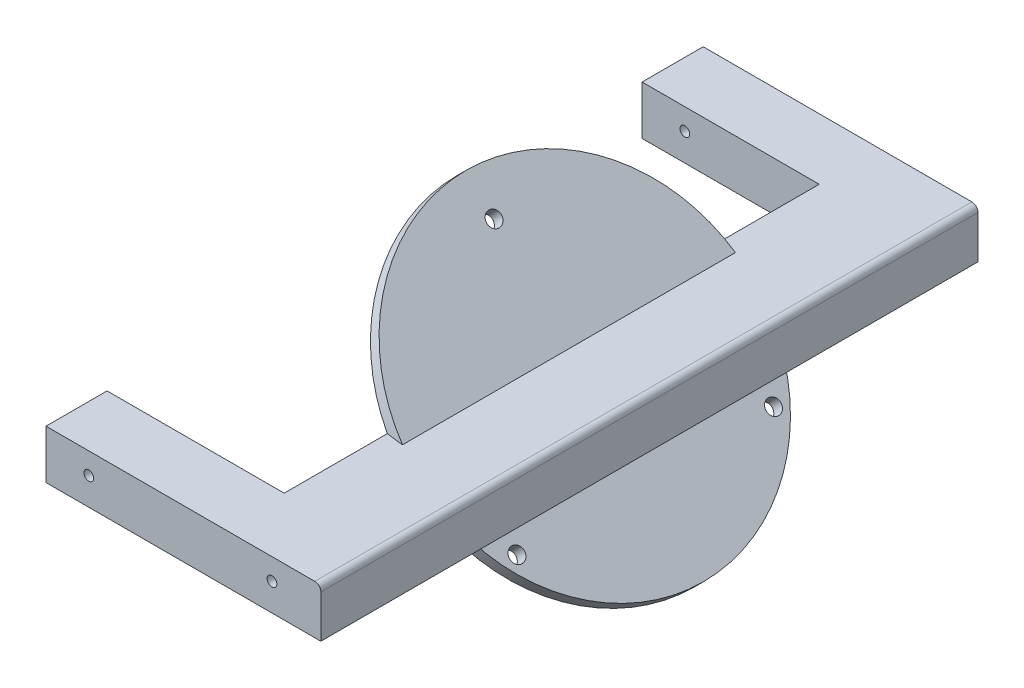
SolidWorks part; units mm, degrees
material "Nylon 101"
ref_plane "Front Plane" through (0, 0, 0) normal (0, 0, 1) x (1, 0, 0)
ref_plane "Top Plane" through (0, 0, 0) normal (0, 1, 0) x (1, 0, 0)
ref_plane "Right Plane" through (0, 0, 0) normal (1, 0, 0) x (0, 0, -1)
sketch "Sketch1" plane through (0, 0, 0) normal (0, 0, 1) x (1, 0, 0)
  line L4 (8, 4) -> (-8, 4)
  line L6 (0, -4) -> (-8, 4)
  line L7 (0, 4) -> (0, -4) construction
  line L8 (8, 4) -> (8, -4)
  line L9 (8, -4) -> (0, -4)
  dimension "D1" = 8
  dimension "D2" = 45
extrude "Base" add sketch "Sketch1" along normal mid plane 107.6
sketch "Sketch4" plane through (-2, -2, 0) normal (-0.7071, -0.7071, 0) x (0, 0, 1)
  line L0 (-53.8, 2.8284) -> (53.8, 2.8284) construction
  line L1 (-53.8, 8.4853) -> (-53.8, -2.8284) construction
  line L2 (53.8, 8.4853) -> (53.8, -2.8284) construction
  line L3 (0, 8.4853) -> (0, -2.8284) construction
  line L4 (53.8, 8.4853) -> (-53.8, 8.4853) construction
  line L6 (53.8, -2.8284) -> (-53.8, -2.8284) construction
  line L7 (-17.5, 20.3284) -> (17.5, 20.3284)
  line L8 (-17.5, 20.3284) -> (-17.5, -14.6716)
  line L9 (-17.5, -14.6716) -> (17.5, -14.6716)
  line L10 (17.5, 20.3284) -> (17.5, -14.6716)
  line L11 (-17.5, 20.3284) -> (17.5, -14.6716) construction
  line L12 (-17.5, -14.6716) -> (17.5, 20.3284) construction
  circle A0 centre (0, 2.8284) radius 27.5
  point P16 (0, 2.8284)
  point P17 (0, 2.8284)
  line M5 (53.8, 8.4853) -> (-53.8, 8.4853)
  dimension "D1" = 55
  dimension "D2" = 35
extrude "Boss-Extrude2" add sketch "Sketch4" against normal blind 2 contours A0 L8 L7 L10 M5 | L10 L7 L8 M5 | A0 L10 L9 L8 | A0 L8 M5 | L10 L8 L9 | L10 L8 M5 | A0 L10 M5 region at (-16.475, 12.475, 0) region at (-12.1872, 8.1872, 0) region at (0.1872, -4.1872, 0) region at (0.1872, -4.1872, -18.1422)
hole_wizard "M2 Clearance Hole1" positions "Sketch5" profile "Sketch6" hole size "M2" standard "ANSI Metric" end condition through all
sketch "Sketch5" plane through (-0.5858, -0.5858, 0) normal (0.7071, 0.7071, 0) x (0.7071, -0.7071, 0)
  line L4 (-8.4853, 0) -> (2.8284, 0) construction
  line L5 (-20.3284, 17.5) -> (-20.3284, -17.5) construction
  line L6 (-20.3284, -17.5) -> (14.6716, -17.5) construction
  line L7 (14.6716, 17.5) -> (14.6716, -17.5) construction
  line L8 (-20.3284, 17.5) -> (14.6716, 17.5) construction
  point P0 (-23.8284, 0)
  point P2 (11.1716, 21)
  point P4 (11.1716, -21)
  dimension "D1" = 3.5
  dimension "D2" = 3.5
  dimension "D3" = 3.5
  dimension "D4" = 3.5
sketch "Sketch6" plane through (-17.435, 16.2635, 0) normal (0, 0, 1) x (-0.7071, 0.7071, 0)
  line L0 (0, 0) -> (0, 29.5)
  line L1 (0, 29.5) -> (1.2, 29.5)
  line L2 (1.2, 29.5) -> (1.2, 0)
  line L5 (1.2, 0) -> (0, 0)
  line L11 (0, -6.35) -> (0, 107.95) construction
  dimension "Thru Hole Dia." = 2.4
  dimension "Thru Hole Depth" = 29.5
ref_plane "Plane1" through (-2, 2, 0) normal (0.7071, -0.7071, 0) x (0, 0, 1)
sketch "Sketch8" plane through (-2, 2, 0) normal (0.7071, -0.7071, 0) x (0, 0, 1)
  line L0 (0, 3.8284) -> (0, 2.8284)
  line L1 (27.5, 2.8284) -> (-27.5, 2.8284) construction
  line L2 (0, 2.8284) -> (-12, 2.8284)
  line L4 (0, 2.8284) -> (0, 10.3284) construction
  line L5 (-6.5, 10.3284) -> (-12, 2.8284)
  arc A1 (-6.5, 10.3284) -> (0, 3.8284) centre (0, 10.3284) ccw
  dimension "D2" = 6.5
  dimension "D1" = 1
  dimension "D3" = 12
revolve "Revolve1" add sketch "Sketch8" angle 360 about L4
fillet "Fillet1" radius 0.5 1 edges at (-13.8995, -0.7071, 0)
hole_wizard "Side Holes" positions "Sketch2" profile "Sketch3" hole size "M2x0.4" standard "ANSI Metric" end condition through all
sketch "Sketch2" plane through (0, 0, 53.8) normal (0, 0, 1) x (1, 0, 0)
  line L0 (0, 0.5) -> (0, 4) construction
  line L1 (8, 4) -> (-8, 4) construction
  line L3 (-4.5, 0.5) -> (8, 0.5) construction
  line L4 (-8, 4) -> (0, -4) construction
  line L6 (8, -4) -> (8, 4) construction
  point P0 (0, 0.5)
  dimension "D1" = 3.5
sketch "Sketch3" plane through (0, 0.5, 53.8) normal (1, 0, 0) x (0, -1, 0)
  line L0 (0, 0) -> (0, 107.6)
  line L1 (0, 107.6) -> (0.8, 107.6)
  line L2 (0.8, 107.6) -> (0.8, 0)
  line L5 (0.8, 0) -> (0, 0)
  line L11 (0, -6.35) -> (0, 107.95) construction
  dimension "Thru Hole Dia." = 1.6
  dimension "Thru Hole Depth" = 107.6
sketch "Sketch9" plane through (0, 0, 53.8) normal (0, 0, 1) x (1, 0, 0)
  line L0 (-8, 4) -> (0, -4)
  line L1 (0, -4) -> (-37, -4)
  line L2 (-37, -4) -> (-37, 4)
  line L3 (-37, 4) -> (-8, 4)
  line L4 (8, -4) -> (8, 4) construction
  dimension "D1" = 45
extrude "Side Arm" add sketch "Sketch9" against normal blind 10
mirror "Mirror1" about plane through (0, 0, 0) normal (0, 0, 1) of "Side Arm"
hole_wizard "Tap Drill for M2x0.4 Tap1" positions "Sketch10" profile "Sketch11" hole size "M2x0.4" standard "ANSI Metric" end condition through all
sketch "Sketch10" plane through (0, 0, 53.8) normal (0, 0, 1) x (1, 0, 0)
  line L0 (-37, 4) -> (-37, -4) construction
  point P0 (-30, 0.5)
  dimension "D1" = 7
sketch "Sketch11" plane through (-30, 0.5, 53.8) normal (1, 0, 0) x (0, -1, 0)
  line L0 (0, 0) -> (0, 107.6)
  line L1 (0, 107.6) -> (0.8, 107.6)
  line L2 (0.8, 107.6) -> (0.8, 0)
  line L5 (0.8, 0) -> (0, 0)
  line L11 (0, -6.35) -> (0, 107.95) construction
  dimension "Thru Hole Dia." = 1.6
  dimension "Thru Hole Depth" = 107.6
fillet "Fillet2" radius 1 1 edges at (8, 4, 0)
